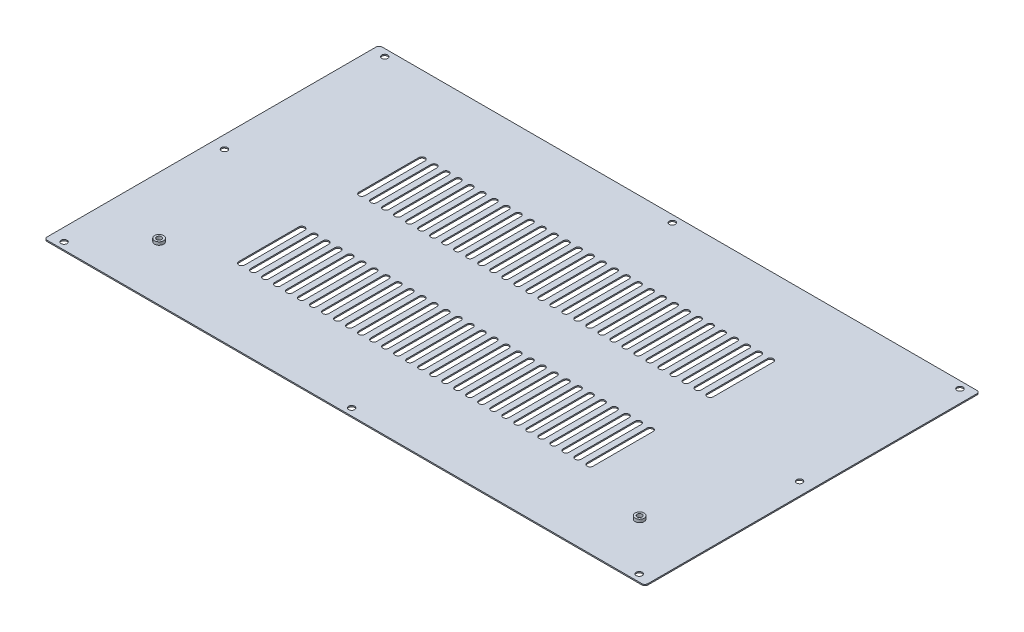
SolidWorks part; units mm, degrees
note: The reader was unsure of these and kept them because the rebuilt part matched: thickness of "基体-法兰1", "钣金6", "钣金7", "钣金8", "钣金10", "钣金12".
ref_plane "前视基准面" through (0, 0, 0) normal (0, 0, 1) x (1, 0, 0)
ref_plane "上视基准面" through (0, 0, 0) normal (0, 1, 0) x (1, 0, 0)
ref_plane "右视基准面" through (0, 0, 0) normal (1, 0, 0) x (0, 0, -1)
sketch "草图1" plane through (0, 0, 0) normal (0, 1, 0) x (1, 0, 0)
  line L0 (0, 180.1871) -> (0, -209.6555) construction
  line L1 (-273.1968, 0) -> (284.2475, 0) construction
  line L2 (-200, 111.5) -> (200, 111.5)
  line L3 (200, 111.5) -> (200, -111.5)
  line L4 (200, -111.5) -> (-200, -111.5)
  line L5 (-200, -111.5) -> (-200, 111.5)
  circle A0 centre (-191.5, 106.8) radius 2
  circle A1 centre (-191.5, -106.8) radius 2
  circle A2 centre (-191.5, 0) radius 2
  circle A3 centre (0, -106.8) radius 2
  circle A4 centre (0, 106.8) radius 2
  circle A5 centre (191.5, 106.8) radius 2
  circle A6 centre (191.5, -106.8) radius 2
  circle A7 centre (191.5, 0) radius 2
  dimension "D3" = 4
  dimension "D1" = 400
  dimension "D2" = 223
  dimension "D4" = 106.8
  dimension "D5" = 191.5
base flange "基体-法兰1" sketch "草图1" thickness 0.8 reverse thickness direction no parameters "D1"=2
sketch "草图6" plane through (0, 0, 0) normal (0, 1, 0) x (1, 0, 0)
  line L0 (0, 200.6049) -> (0, -189.0678) construction
  line L1 (-267.6394, 0) -> (401.5148, 0) construction
  line L2 (-120, 60) -> (-120, 20) construction
  line L3 (-118, 60) -> (-118, 20)
  line L4 (-122, 60) -> (-122, 20)
  line L5 (-200, 111.5) -> (-200, -111.5) construction
  arc A0 (-118, 60) -> (-122, 60) centre (-120, 60) ccw
  arc A1 (-122, 20) -> (-118, 20) centre (-120, 20) ccw
  point P7 (-120, 40)
  dimension "D4" = 2
  dimension "D1" = 80
  dimension "D2" = 40
  dimension "D3" = 40
extrude "切除-拉伸1" cut sketch "草图6" against normal through all normal cut yes
pattern_linear "阵列(线性)1" count 30 spacing 8 along (1, 0, 0) count 2 spacing 80 along (0, 0, 1) of "切除-拉伸1"
fillet "圆角1" radius 2 4 edges at (200, -0.4, -111.5) (200, -0.4, 111.5) (-200, -0.4, 111.5) (-200, -0.4, -111.5)
sketch "草图7" plane through (0, 0, 0) normal (0, 1, 0) x (1, 0, 0)
  line L0 (-270.1817, 0) -> (285.7324, 0) construction
  line L1 (0, 170.9989) -> (0, -179.0159) construction
  circle A0 centre (-160, 75) radius 3 construction
  circle A1 centre (-160, -75) radius 3
  circle A2 centre (160, 75) radius 3 construction
  circle A3 centre (160, -75) radius 3
  dimension "D3" = 6
  dimension "D1" = 150
  dimension "D2" = 320
extrude "凸台-拉伸1" add sketch "草图7" along normal blind 2
hole_wizard "M4 螺纹孔1" positions "草图8" profile "草图9" tap size "M4" standard "GB"
sketch "草图8" plane through (0, -0.8, 0) normal (0, -1, 0) x (-1, 0, 0)
  point P0 (160, -75)
  point P2 (-160, -75)
sketch "草图9" plane through (-160, -0.8, 75) normal (1, 0, 0) x (0, 0, -1)
  line L0 (0, 0) -> (0, 12.4914)
  line L1 (0, 12.4914) -> (1.65, 11.5)
  line L2 (1.65, 11.5) -> (1.65, 0)
  line L5 (1.65, 0) -> (0, 0)
  line L10 (0, 12.4914) -> (-1.65, 11.5) construction
  line L11 (0, -6.35) -> (0, 107.95) construction
  dimension "螺纹孔钻头直径" = 3.3
  dimension "螺纹孔钻头深度" = 11.5
  dimension "导头角度" = 118
cosmetic thread "孔螺蚊线3"
cosmetic thread "孔螺蚊线4"
sketch "折弯-线1" plane through (0, 0, 0) normal (0, 1, 0) x (1, 0, 0)
sketch "边界框1" plane through (0, 0, 0) normal (0, 1, 0) x (1, 0, 0)
sheet metal parameters "钣金6" thickness 0.8 parameters "D1"=2, "D7"=1
flat pattern "平板型式6" [suppressed]
sketch "折弯-线2" plane through (0, 0, 0) normal (0, 1, 0) x (1, 0, 0)
sketch "边界框2" [suppressed] plane through (0, 0, 0) normal (0, 1, 0) x (1, 0, 0)
sheet metal parameters "钣金7" thickness 0.8 parameters "D1"=2, "D7"=1
flat pattern "平板型式6"
sketch "折弯-线2" plane through (0, 0, 0) normal (0, 1, 0) x (1, 0, 0)
sketch "边界框2" [suppressed] plane through (0, 0, 0) normal (0, 1, 0) x (1, 0, 0)
sheet metal parameters "钣金8" thickness 0.8 parameters "D1"=2, "D7"=1
flat pattern "平板型式6"
sketch "折弯-线2" plane through (0, 0, 0) normal (0, 1, 0) x (1, 0, 0)
sketch "边界框2" [suppressed] plane through (0, 0, 0) normal (0, 1, 0) x (1, 0, 0)
sheet metal parameters "钣金10" thickness 0.8 parameters "D1"=2, "D7"=1
flat pattern "平板型式6"
sketch "折弯-线2" plane through (0, 0, 0) normal (0, 1, 0) x (1, 0, 0)
sketch "边界框2" [suppressed] plane through (0, 0, 0) normal (0, 1, 0) x (1, 0, 0)
sheet metal parameters "钣金12" thickness 0.8 parameters "D1"=2, "D7"=1
flat pattern "平板型式6"
sketch "折弯-线2" plane through (0, 0, 0) normal (0, 1, 0) x (1, 0, 0)
sketch "边界框2" [suppressed] plane through (0, 0, 0) normal (0, 1, 0) x (1, 0, 0)
